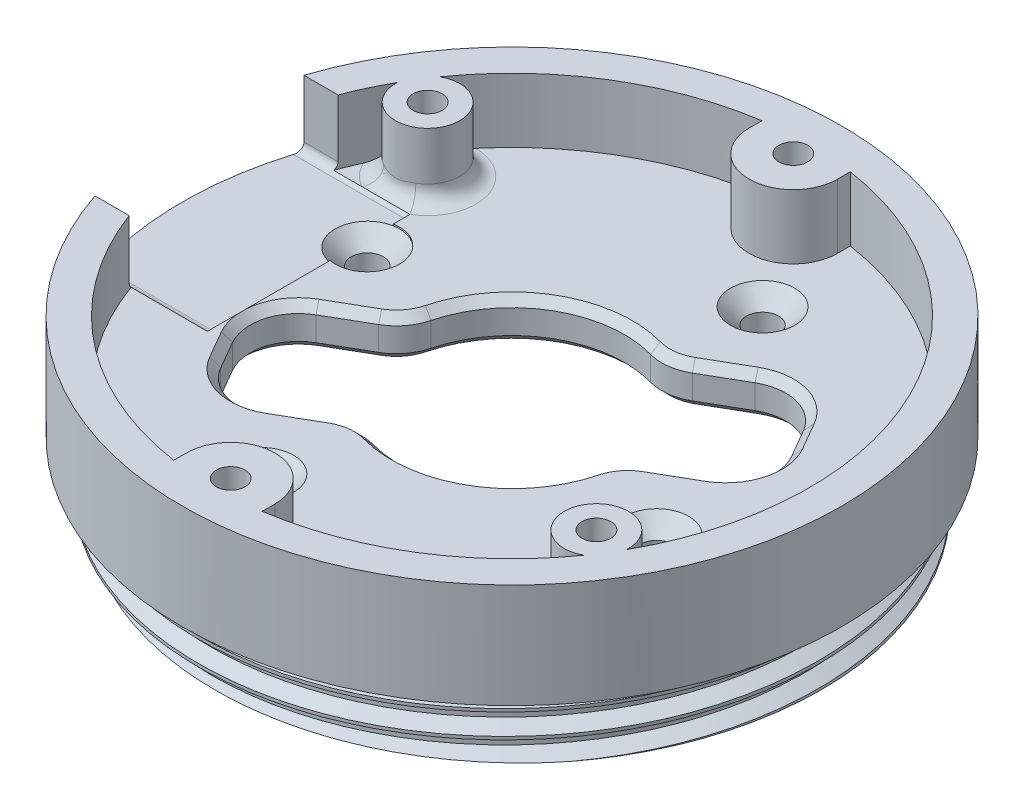
SolidWorks part; units mm, degrees
ref_plane "Front plane" through (0, 0, 0) normal (0, 0, 1) x (1, 0, 0)
ref_plane "Top plane" through (0, 0, 0) normal (0, 1, 0) x (1, 0, 0)
ref_plane "Right plane" through (0, 0, 0) normal (1, 0, 0) x (0, 0, -1)
ref_axis "Axis X" through (0, 0, 0) along (1, 0, 0)
ref_axis "Axis Y" through (0, 0, 0) along (0, 1, 0)
ref_axis "Axis Z" through (0, 0, 0) along (0, 0, 1)
sketch "Sketch1" plane through (0, 0, 0) normal (0, 1, 0) x (1, 0, 0)
  line L0 (0, 0) -> (0, 20.5) construction
  circle A0 centre (0, 0) radius 20.5
  circle A8 centre (0, 0) radius 7
  circle A9 centre (0, 0) radius 17.5 construction
  circle A10 centre (0, 17.5) radius 0.9
  circle A11 centre (0, -17.5) radius 0.9
  circle A12 centre (0, 0) radius 13.5 construction
  dimension "D1" = 41
  dimension "D9" = 14
  dimension "D10" = 35
  dimension "D11" = 1.8
  dimension "D12" = 1.8
  dimension "D5" = 27
extrude "Extrude1" add sketch "Sketch1" along normal blind 2.5
sketch "Sketch3" plane through (0, 2.5, 0) normal (0, 1, 0) x (1, 0, 0)
  line L0 (-2.75, 17.5) -> (-2.75, 18.2945)
  line L1 (2.75, 17.5) -> (2.75, 18.2945)
  line L2 (2.75, -17.5) -> (2.75, -18.2945)
  line L3 (-2.75, -17.5) -> (-2.75, -18.2945)
  line L5 (14.15, 8.9) -> (-14.15, 8.9) construction
  line L6 (14.15, 8.9) -> (14.15, -8.9) construction
  line L7 (14.15, -8.9) -> (-14.15, -8.9) construction
  line L8 (-14.15, 8.9) -> (-14.15, -8.9) construction
  line L9 (14.15, 8.9) -> (-14.15, -8.9) construction
  line L10 (14.15, -8.9) -> (-14.15, 8.9) construction
  arc A0 (-2.75, 18.2945) -> (-2.75, -18.2945) centre (0, 0) ccw
  circle A1 centre (0, 17.5) radius 0.9
  circle A2 centre (0, 0) radius 20.5 construction
  arc A3 (-2.75, 17.5) -> (2.75, 17.5) centre (0, 17.5) ccw
  arc A4 (2.75, -17.5) -> (-2.75, -17.5) centre (0, -17.5) ccw
  circle A5 centre (0, 0) radius 20.5
  arc A6 (-2.6272, -18.3125) -> (2.6272, -18.3125) centre (0, -17.5) ccw construction
  arc A7 (2.6272, 18.3125) -> (-2.6272, 18.3125) centre (0, 17.5) ccw construction
  arc A8 (2.6272, 18.3125) -> (-2.6272, 18.3125) centre (0, 0) ccw construction
  arc A9 (2.75, -18.2945) -> (2.75, 18.2945) centre (0, 0) ccw
  arc A10 (-2.6272, -18.3125) -> (2.6272, -18.3125) centre (0, 0) ccw construction
  circle A11 centre (0, -17.5) radius 0.9
  arc A12 (2.75, 18.2945) -> (2.6272, 18.3125) centre (0, 0) ccw construction
  arc A13 (2.75, 17.5) -> (2.6272, 18.3125) centre (0, 17.5) ccw construction
  arc A14 (-2.6272, 18.3125) -> (-2.75, 18.2945) centre (0, 0) ccw construction
  arc A15 (-2.6272, 18.3125) -> (-2.75, 17.5) centre (0, 17.5) ccw construction
  arc A16 (-2.75, -17.5) -> (-2.6272, -18.3125) centre (0, -17.5) ccw construction
  arc A17 (-2.75, -18.2945) -> (-2.6272, -18.3125) centre (0, 0) ccw construction
  arc A18 (2.6272, -18.3125) -> (2.75, -17.5) centre (0, -17.5) ccw construction
  arc A19 (2.6272, -18.3125) -> (2.75, -18.2945) centre (0, 0) ccw construction
  circle A20 centre (-14.15, 8.9) radius 2 construction
  circle A21 centre (14.15, -8.9) radius 2.2569 construction
  dimension "D2" = 5.5
  dimension "D3" = 5.5
  dimension "D5" = 1.8
  dimension "D6" = 1.8
  dimension "D9" = 4
  dimension "D10" = 4.5137
  dimension "D7" = 28.3
  dimension "D8" = 17.8
extrude "Extrude2" add sketch "Sketch3" along normal blind 4
sketch "Sketch7" plane through (0, 6.5, 0) normal (0, 1, 0) x (1, 0, 0)
  line L0 (0, 0) -> (-20.5, 0) construction
  line L1 (-16.9115, 7.5) -> (-16.9115, -7.5) construction
  line L2 (-15, 10.8282) -> (-15, -10.8282)
  circle A0 centre (0, 0) radius 20.5 construction
  arc A1 (-2.75, 18.2945) -> (-2.75, -18.2945) centre (0, 0) ccw construction
  arc A2 (-2.75, 18.2945) -> (-2.75, -18.2945) centre (0, 0) ccw construction
  arc A4 (-15, 10.8282) -> (-15, -10.8282) centre (0, 0) ccw
  arc A5 (-15, -10.8282) -> (-15, 10.8282) centre (0, 0) ccw construction
  dimension "D1" = 15
  dimension "D4" = 15
extrude "Extrude8" [suppressed] add sketch "Sketch7" against normal through all
sketch "Sketch4" plane through (0, 6.5, 0) normal (0, 1, 0) x (1, 0, 0)
  line L0 (0, 0) -> (-20.5, 0) construction
  line L1 (-20.5, 7.5) -> (-20.5, -7.5)
  line L3 (-12.65, 6.5) -> (-12.65, -6.5)
  line L6 (-20.5, 7.5) -> (-19.65, 7.5)
  line L8 (-19.65, 6.5) -> (-12.65, 6.5)
  line L9 (-19.65, -6.5) -> (-12.65, -6.5)
  line L10 (-20.5, -7.5) -> (-19.65, -7.5)
  line L11 (-19.65, 6.5) -> (-19.65, -6.5) construction
  line L12 (-19.65, 7.5) -> (-19.65, 6.5)
  line L13 (-19.65, -6.5) -> (-19.65, -7.5)
  circle A0 centre (0, 0) radius 20.5 construction
  point P11 (-20.5, 0)
  point P15 (-19.65, -7.5)
  point P19 (-12.65, 0)
  point P21 (-19.65, 7.5)
  dimension "D2" = 15
  dimension "D3" = 13
  dimension "D5" = 19.65
  dimension "D1" = 7
extrude "Extrude3" cut sketch "Sketch4" against normal blind 4.1
sketch "Sketch9" plane through (0, 0, 0) normal (0, -1, 0) x (1, 0, 0)
  circle A0 centre (0, 17.5) radius 1
  circle A1 centre (0, -17.5) radius 1
  dimension "D1" = 2
  dimension "D2" = 2
extrude "Extrude5" add sketch "Sketch9" against normal blind 1
sketch "Sketch8" plane through (0, 0, 0) normal (0, -1, 0) x (1, 0, 0)
  circle A0 centre (0, 0) radius 17.5
  circle A1 centre (0, 0) radius 18.45
  dimension "D1" = 35
  dimension "D2" = 0.95
extrude "Extrude6" add sketch "Sketch8" along normal blind 4
thread "Thread1" pitch 1.5 method extrude trim with start face yes trim with end face yes profile "Sketch11" start angle 0, offset 2, length 0, pitch 1.5, diameter 36.9
ref_plane "Plane1" through (18.45, -6, 0) normal (0, 0, 1) x (1, 0, 0)
sketch "Sketch11" plane through (18.45, -6, 0) normal (0, 0, 1) x (1, 0, 0)
  line L0 (0, 0) -> (0, 1.5) construction
  line L1 (0, 0) -> (0.8119, 0.4687)
  line L2 (0.8119, 0.4687) -> (0.8119, 0.6562)
  line L3 (0.8119, 0.6562) -> (0, 1.125)
  line L4 (0.8119, 0.5625) -> (0, 0.5625) construction
  line L11 (0, 0) -> (0, 1.125)
  point P2 (0, 0)
  dimension "Pitch" = 1.5
  dimension "Profile_Angle" = 60
  dimension "Profile_Land" = 0.1875
  dimension "Profile_Height" = 0.8119
fillet "Fillet3" [suppressed] radius 0.5
sketch "Sketch28" plane through (0, 2.4, 0) normal (0, 1, 0) x (1, 0, 0)
  line L0 (-17.3205, 6.5) -> (-17.3205, -6.5)
  arc A0 (-17.3205, 6.5) -> (-17.3205, -6.5) centre (0, 0) ccw
  arc A1 (-17.3205, -6.5) -> (-17.3205, 6.5) centre (0, 0) ccw construction
extrude "Extrude15" [suppressed] add sketch "Sketch28" against normal up to surface (0.6 mm away)
fillet "Fillet4" radius 0.5 2 edges at (-16.0461, 2.4, 6.5) (-16.0461, 2.4, -6.5)
sketch "Sketch22" plane through (0, 2.5, 0) normal (0, 1, 0) x (1, 0, 0)
  line L1 (14.15, 8.9) -> (-14.15, 8.9) construction
  line L2 (14.15, 8.9) -> (14.15, -8.9) construction
  line L3 (14.15, -8.9) -> (-14.15, -8.9) construction
  line L4 (-14.15, 8.9) -> (-14.15, -8.9) construction
  line L5 (14.15, 8.9) -> (-14.15, -8.9) construction
  line L6 (14.15, -8.9) -> (-14.15, 8.9) construction
  circle A1 centre (-14.15, 8.9) radius 2
  circle A2 centre (14.15, -8.9) radius 2
  point P0 (0, 0)
  dimension "D3" = 4
  dimension "D4" = 4
  dimension "D1" = 28.3
  dimension "D2" = 17.8
extrude "Extrude9" add sketch "Sketch22" along normal blind 4
sketch "Sketch23" plane through (0, 6.5, 0) normal (0, 1, 0) x (1, 0, 0)
  line L0 (0, 0) -> (3.2942, 12.2942) construction
  line L1 (0, 0) -> (0, 12.7279) construction
  line L6 (0, 0) -> (9.4981, -8.8746) construction
  circle A0 centre (14.15, -8.9) radius 0.9
  circle A1 centre (-14.15, 8.9) radius 0.9
  circle A2 centre (0, 0) radius 12.7279 construction
  circle A4 centre (3.2942, 12.2942) radius 1
  circle A5 centre (12.2942, -3.2942) radius 1
  circle A6 centre (-3.2942, -12.2942) radius 1
  circle A7 centre (-12.2942, 3.2942) radius 1
  point P21 (0, 0)
  dimension "D1" = 1.8
  dimension "D2" = 1.8
  dimension "D4" = 25.4558
  dimension "D5" = 2
  dimension "D3" = 15
extrude "Extrude10" cut sketch "Sketch23" against normal through all
sketch "Sketch24" plane through (0, 2.5, 0) normal (0, 1, 0) x (1, 0, 0)
  line L0 (3.2942, 12.2942) -> (0, 0) construction
  line L1 (8.6603, 5) -> (-8.6603, -5) construction
  line L2 (7.6603, 6.7321) -> (9.6603, 3.2679) construction
  line L3 (10.2583, 8.2321) -> (12.2583, 4.7679)
  line L4 (5.0622, 5.2321) -> (7.0622, 1.7679)
  line L5 (0, 0) -> (3.9532, -6.8471) construction
  line L6 (-9.6603, -3.2679) -> (-7.6603, -6.7321) construction
  line L7 (-12.2583, -4.7679) -> (-10.2583, -8.2321)
  line L8 (-7.0622, -1.7679) -> (-5.0622, -5.2321)
  arc A0 (10.2583, 8.2321) -> (5.0622, 5.2321) centre (7.6603, 6.7321) ccw
  arc A1 (7.0622, 1.7679) -> (12.2583, 4.7679) centre (9.6603, 3.2679) ccw
  arc A2 (-12.2583, -4.7679) -> (-7.0622, -1.7679) centre (-9.6603, -3.2679) cw
  arc A3 (-5.0622, -5.2321) -> (-10.2583, -8.2321) centre (-7.6603, -6.7321) cw
  circle A4 centre (3.2942, 12.2942) radius 1 construction
  point P6 (0, 0)
  point P9 (8.6603, 5)
  point P17 (-8.6603, -5)
  dimension "D3" = 4
  dimension "D1" = 10
  dimension "D2" = 6
  dimension "D4" = 45
extrude "Extrude11" [suppressed] cut sketch "Sketch24" against normal blind 40
chamfer "Chamfer1" [suppressed] distance 0.5 angle 45
sketch "Sketch25" plane through (0, 2.5, 0) normal (0, 1, 0) x (1, 0, 0)
  line L0 (9.2583, 9.9641) -> (-13.2583, -3.0359)
  line L1 (9.2583, 9.9641) -> (13.2583, 3.0359)
  line L2 (-13.2583, -3.0359) -> (-9.2583, -9.9641)
  line L3 (13.2583, 3.0359) -> (-9.2583, -9.9641)
  line L4 (9.2583, 9.9641) -> (-9.2583, -9.9641) construction
  line L5 (-13.2583, -3.0359) -> (13.2583, 3.0359) construction
  line L6 (0, 0) -> (3.2942, 12.2942) construction
  circle A0 centre (3.2942, 12.2942) radius 1 construction
  point P1 (0, 0)
  dimension "D1" = 26
  dimension "D2" = 45
  dimension "D3" = 8
extrude "Extrude12" cut sketch "Sketch25" against normal through all
fillet "Fillet5" radius 3 8 edges at (6.9749, 1.25, 0.5918) (2.9749, 1.25, -6.3364) (-6.9749, 1.25, -0.5918) (-2.9749, 1.25, 6.3364) (-9.2583, 1.25, 9.9641) (-13.2583, 1.2, 3.0359) (13.2583, 1.25, -3.0359) (9.2583, 1.25, -9.9641)
chamfer "Chamfer2" distance 0.5 angle 45 32 edges at (-9.4225, 0, 0.8213) (-12.058, 0, 3.3575) (-7.2955, 0, -0.6771) (-11.2583, 0, 6.5) (-3.5, 0, -6.0622) (-8.9367, 0, 8.7638) (3.0614, 0, -6.6566) (-5.4225, 0, 7.7495) (5.4225, 0, -7.7495) (-3.0614, 0, 6.6566) (8.9367, 0, -8.7638) (3.5, 0, 6.0622) (11.2583, 0, -6.5) (7.2955, 0, 0.6771) (12.058, 0, -3.3575) (9.4225, 0, -0.8213) (-3.0614, 2.5, 6.6566) (-5.4225, 2.5, 7.7495) (3.5, 2.5, 6.0622) (-8.9367, 2.5, 8.7638) (7.2955, 2.5, 0.6771) (-11.2583, 2.5, 6.5) (9.4225, 2.5, -0.8213) (-12.058, 2.5, 3.3575) (12.058, 2.5, -3.3575) (-9.4225, 2.5, 0.8213) (11.2583, 2.5, -6.5) (-7.2955, 2.5, -0.6771) (8.9367, 2.5, -8.7638) (-3.5, 2.5, -6.0622) (5.4225, 2.5, -7.7495) (3.0614, 2.5, -6.6566)
sketch "Sketch27" plane through (0, 2.5, 0) normal (0, 1, 0) x (1, 0, 0)
  line L0 (10.2942, -1.2942) -> (14.2942, -1.2942)
  line L1 (1.2942, 10.2942) -> (5.2942, 10.2942)
  line L2 (1.2942, 10.2942) -> (1.2942, 14.2942)
  line L3 (1.2942, 14.2942) -> (5.2942, 14.2942)
  line L4 (5.2942, 10.2942) -> (5.2942, 14.2942)
  line L5 (1.2942, 10.2942) -> (5.2942, 14.2942) construction
  line L6 (1.2942, 14.2942) -> (5.2942, 10.2942) construction
  line L7 (14.2942, -1.2942) -> (14.2942, -5.2942)
  line L8 (10.2942, -5.2942) -> (14.2942, -5.2942)
  line L9 (10.2942, -1.2942) -> (10.2942, -5.2942)
  line L10 (14.2942, -1.2942) -> (10.2942, -5.2942) construction
  line L11 (10.2942, -1.2942) -> (14.2942, -5.2942) construction
  line L12 (-1.2942, -10.2942) -> (-1.2942, -14.2942)
  line L13 (-1.2942, -14.2942) -> (-5.2942, -14.2942)
  line L14 (-5.2942, -10.2942) -> (-5.2942, -14.2942)
  line L15 (-1.2942, -10.2942) -> (-5.2942, -10.2942)
  line L16 (-1.2942, -14.2942) -> (-5.2942, -10.2942) construction
  line L17 (-1.2942, -10.2942) -> (-5.2942, -14.2942) construction
  line L18 (-10.2942, 1.2942) -> (-14.2942, 1.2942)
  line L19 (-14.2942, 1.2942) -> (-14.2942, 5.2942)
  line L20 (-10.2942, 5.2942) -> (-14.2942, 5.2942)
  line L21 (-10.2942, 1.2942) -> (-10.2942, 5.2942)
  line L22 (-14.2942, 1.2942) -> (-10.2942, 5.2942) construction
  line L23 (-10.2942, 1.2942) -> (-14.2942, 5.2942) construction
  circle A0 centre (3.2942, 12.2942) radius 2 construction
  circle A1 centre (3.2942, 12.2942) radius 1 construction
  circle A2 centre (12.2942, -3.2942) radius 2 construction
  circle A3 centre (-3.2942, -12.2942) radius 2 construction
  circle A4 centre (-12.2942, 3.2942) radius 2 construction
  circle A5 centre (-3.2942, -12.2942) radius 1 construction
  point P30 (0, 0)
  dimension "D1" = 1
  dimension "D2" = 4
extrude "Extrude14" [suppressed] cut sketch "Sketch27" along normal through all
chamfer "Chamfer3" distance 1 angle 45 3 edges at (-3.2942, 2.5, 13.2942) (12.2942, 2.5, 4.2942) (3.2942, 2.5, -11.2942)
fillet "Fillet6" radius 1 2 edges at (12.457, 2.5, 7.8352) (-12.457, 2.5, -7.8352)
fillet "Fillet7" [suppressed] radius 0.5
sketch "Эскиз2" plane through (0, 2.4, 0) normal (0, 1, 0) x (1, 0, 0)
  circle A0 centre (-12.2942, 3.2942) radius 2
  circle A2 centre (-12.2942, 3.2942) radius 1 construction
  dimension "D1" = 1
extrude "Вырез-Вытянуть1" cut sketch "Эскиз2" along normal up to surface (0.1 mm away) up to face at (3.2942, 2.5, -10.2942)
chamfer "Фаска1" distance 1 angle 45 1 edges at (-12.2942, 2.4, -4.2942)
equation "\"motor_D\"= 30'Motor diameter"
equation "\"motor_H\"= 13'Motor heigh"
equation "\"motor_d1\"= 25.4558'Seating diameter of screws on the fixed part of the motor"
equation "\"motor_s1\"= 2'Screws diameter on the fixed part of motor"
equation "\"motor_d2\"= 0'Seating diameter of screws on the moving part of the motor (if this parameter is not determine, write 0)"
equation "\"motor_s2\"= 2'Screws diameter on the moving part of motor"
equation "\"motor_Dc\"= 5'Central hole diameter of motor"
equation "\"bearing_d1\"= 6'Bearing inner diameter"
equation "\"bearing_d2\"= 17'Bearing external diameter"
equation "\"bearing h\"= 6'Bearing heigh"
equation "\"pin_d\"= 2'Pin diameter"
equation "\"pin_h\"= 12'Pin heigh"
equation "\"D1@Sketch1\" = IIF ( \"motor_D\" < 34 , 41 , \"motor_D\" + 8 )"
equation "\"D9@Sketch1\"=\"motor_cmd\"+2"
equation "\"D10@Sketch1\"=\"D1@Sketch1\"-6"
equation "\"D4@Sketch3\"=\"D1@Sketch3\""
equation "\"D6@Sketch3\"=\"D5@Sketch3\""
equation "\"D5@Sketch1\"=\"motor_D\"*0.9"
equation "\"D1@Sketch8\" = IIF ( \"motor_D\" < 34 , 41 , \"motor_D\" + 8 ) - ( 42 - 36 )"
equation "\"D6@Thread1\"=\"motor_D\"+1.5+2"
equation "\"D4@Sketch7\"= IIF ( \"motor_D\" < 36 , 15 , 18 )"
equation "\"Extrude8\" = IIF ( \"motor_D\" < 36 , \"suppressed\" , \"unsuppressed\" )"
equation "\"motor_a2\"= 10'Seating parameter in rectangle of screws on the moving part of the motor"
equation "\"magnet_d1\"= 5'Magnet inner diameter"
equation "\"magnet_d2\"= 9.5'Magnet external diameter"
equation "\"magnet_h\"= 3'Magnet heigh"
equation "\"motor_b2\"= 22'Seating parameter in rectangle of screws on the moving part of the motor"
equation "\"motor_cmd\"= 12'Central magnet mount diameter"
equation "\"motor_cmh\"= 1.4'Central magnet mount heigh (if not write 0)"
equation "\"motor_whR\"= 10'Distance from center of motor to wires"
equation "\"D1@Extrude2\" = IIF ( \"motor_cmh\" = 0 , \"magnet_h\" + 1.5 + 3.6 - \"D1@Extrude1\" , \"motor_cmh\" + 1.5 + 3.6 - \"D1@Extrude1\" )"
equation "\"D1@Extrude1\"=2.5"
equation "\"D2@Sketch8\"=0.95"
equation "\"print_offset\"= 0.2'Offset for printing holes"
equation "\"D12@Sketch1\"=2-\"print_offset\""
equation "\"D11@Sketch1\"=\"D12@Sketch1\""
equation "\"D5@Sketch3\"=2-\"print_offset\""
equation "\"D5@Sketch4\"=19.65"
equation "\"Fillet3\"= IIF ( \"motor_D\" < 36 , \"suppressed\" , \"unsuppressed\" )"
equation "\"D3@Sketch22\"=\"D4@Sketch22\""
equation "\"D1@Extrude9\"= \"D1@Extrude2\""
equation "\"D1@Sketch23\"=2-\"print_offset\""
equation "\"D2@Sketch23\"=\"D1@Sketch23\""
equation "\"D4@Sketch23\"=\"motor_d1\""
equation "\"D5@Sketch23\"=\"motor_s1\""
equation "\"D1@Sketch24\"=\"motor_whR\""
equation "\"Extrude11\"= IIF ( ( \"motor_whR\" - 3 ) - \"motor_cmd\" < 1 , \"suppressed\" , \"unsuppressed\" )"
equation "\"Chamfer1\"= IIF ( ( \"motor_whR\" - 3 ) - \"motor_cmd\" < 1 , \"suppressed\" , \"unsuppressed\" )"
equation "\"D1@Sketch25\"=\"motor_cmd\"+8+6"
equation "\"Extrude12\"= IIF ( ( \"motor_whR\" - 3 ) - \"motor_cmd\" > 1 , \"suppressed\" , \"unsuppressed\" )"
equation "\"Fillet5\"= IIF ( ( \"motor_whR\" - 3 ) - \"motor_cmd\" > 1 , \"suppressed\" , \"unsuppressed\" )"
equation "\"Chamfer2\"= IIF ( ( \"motor_whR\" - 3 ) - \"motor_cmd\" > 1 , \"suppressed\" , \"unsuppressed\" )"
equation "\"Fillet7\"= IIF ( ( \"motor_d1\" + \"motor_s1\" + 2 ) / 2 > 18 , \"unsuppressed\" , \"suppressed\" )"
equation "\"Extrude14\"= IIF ( ( \"motor_d1\" + \"motor_s1\" + 2 ) / 2 > 18 , \"unsuppressed\" , \"suppressed\" )"
equation "\"ft_sensor_d1\"= 9.8"
equation "\"ft_sensor_d2\"= 24.9"
equation "\"ft_sensor_d3\"= 22.6'Inner diameter of "
equation "\"ft_sensor_h\"= 7.1"
equation "\"ft_sensor_whD\" = 5"
equation "\"Extrude15\"= IIF ( \"motor_cmh\" = 0 , \"unsuppressed\" , \"suppressed\" )"
equation "\"Вырез-Вытянуть1\"= IIF ( \"motor_d1\" + \"motor_s1\" > 13.8 * 2 , \"suppressed\" , \"unsuppressed\" )"
equation "\"Extrude3\"= IIF ( \"motor_D\" < 34 , \"unsuppressed\" , \"suppressed\" )"
